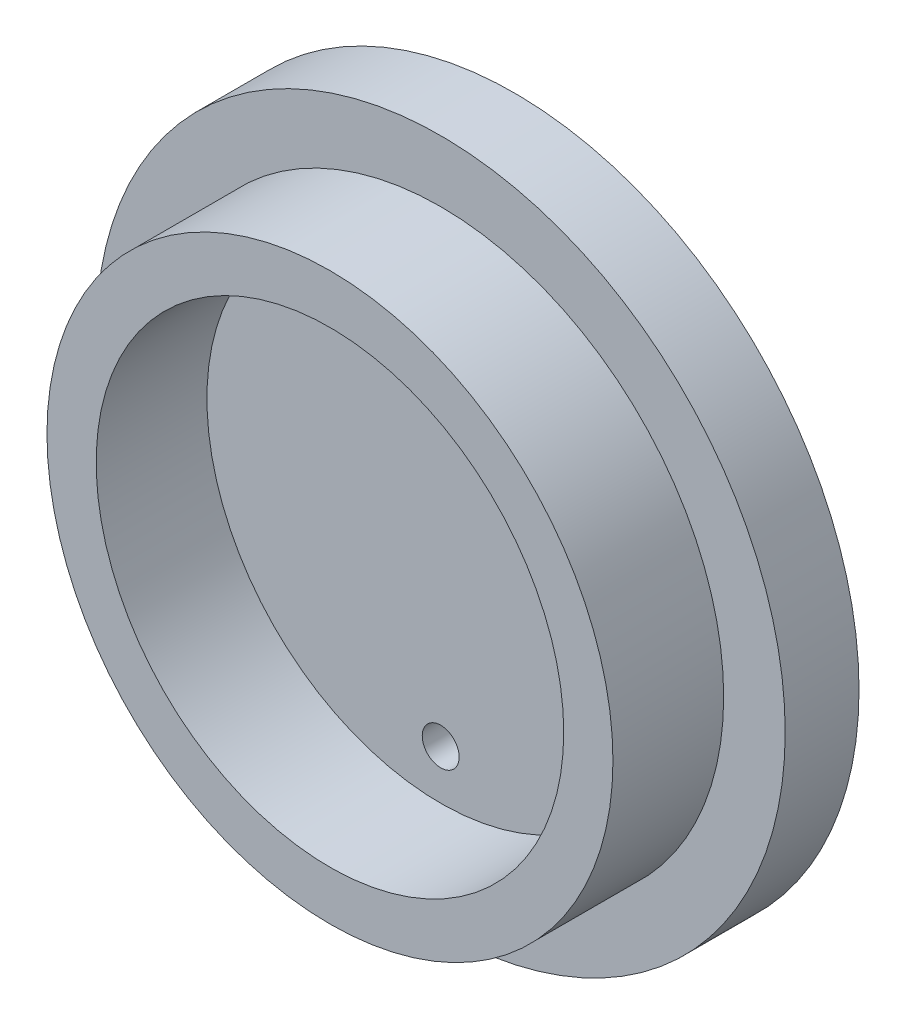
SolidWorks part; units mm, degrees
ref_plane "Front Plane" through (0, 0, 0) normal (0, 0, 1) x (1, 0, 0)
ref_plane "Top Plane" through (0, 0, 0) normal (0, 1, 0) x (1, 0, 0)
ref_plane "Right Plane" through (0, 0, 0) normal (1, 0, 0) x (0, 0, -1)
sketch "Sketch1" plane through (0, 0, 0) normal (0, 0, 1) x (1, 0, 0)
  circle A0 centre (0, 0) radius 28
  circle A1 centre (0, 0) radius 23
  circle A2 centre (0, 0) radius 19
  dimension "D1" = 56
  dimension "D2" = 46
  dimension "D3" = 4
extrude "Boss-Extrude1" add sketch "Sketch1" along normal blind 6 contours A0 A1 | A1 A2 | A2 region at (-27.208, 0, 0) region at (-22.3495, 0, 0) region at (0, 0, 0)
extrude "Boss-Extrude2" add sketch "Sketch1<3>" along normal blind 15 contours A1 A2 region at (-22.3495, 0, 0)
sketch "Sketch1<3>" plane through (0, 0, 0) normal (0, 0, 1) x (1, 0, 0) same geometry as "Sketch1"
sketch "Sketch2" plane through (0, 0, 0) normal (0, 0, -1) x (-1, 0, 0)
  circle A0 centre (0, -15) radius 1.5
  point P2 (0, -15)
  dimension "D1" = 3
  dimension "D2" = 15
extrude "Cut-Extrude1" cut sketch "Sketch2" against normal through all
